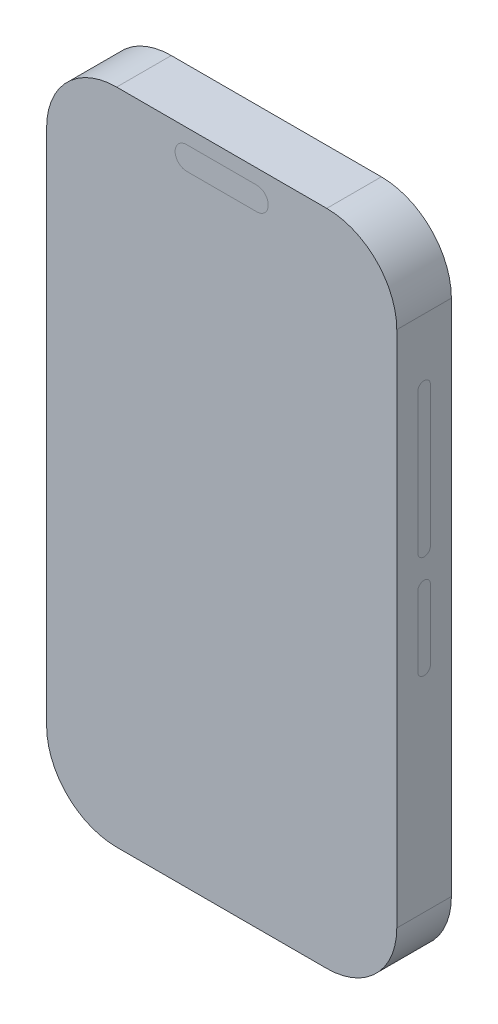
SolidWorks part; units mm, degrees
ref_plane "前视基准面" through (0, 0, 0) normal (0, 0, 1) x (1, 0, 0)
ref_plane "上视基准面" through (0, 0, 0) normal (0, 1, 0) x (1, 0, 0)
ref_plane "右视基准面" through (0, 0, 0) normal (1, 0, 0) x (0, 0, -1)
other "Configuration Table"
sketch "草图2" plane through (0, 0, 0) normal (0, 0, 1) x (1, 0, 0)
  line L1 (-15, 47) -> (15, 47)
  line L2 (-25, 37) -> (-25, -37)
  line L3 (-15, -47) -> (15, -47)
  line L4 (25, 37) -> (25, -37)
  line L5 (-25, 47) -> (25, -47) construction
  line L6 (-25, -47) -> (25, 47) construction
  arc A0 (15, 47) -> (25, 37) centre (15, 37) cw
  arc A1 (-25, -37) -> (-15, -47) centre (-15, -37) ccw
  arc A2 (-15, 47) -> (-25, 37) centre (-15, 37) ccw
  arc A3 (15, -47) -> (25, -37) centre (15, -37) ccw
  point P0 (0, 0)
  dimension "D3" = 10
  dimension "D1" = 50
  dimension "D2" = 94
extrude "凸台-拉伸1" add sketch "草图2" along normal blind 7.8
sketch "草图3" plane through (0, 0, 7.8) normal (0, 0, 1) x (1, 0, 0)
  line L0 (-5, 43.229) -> (5, 43.229) construction
  line L1 (-5, 44.879) -> (5, 44.879)
  line L2 (-5, 41.579) -> (5, 41.579)
  arc A0 (-5, 44.879) -> (-5, 41.579) centre (-5, 43.229) ccw
  arc A1 (5, 41.579) -> (5, 44.879) centre (5, 43.229) ccw
  point P2 (0, 43.229)
  point P7 (0, 0)
  point P8 (0, 0)
split line "分割线1"
sketch "草图7" plane through (25, 0, 0) normal (1, 0, 0) x (0, 0, -1)
  line L0 (-3.8962, 27.8442) -> (-3.8962, 7.8442) construction
  line L1 (-2.9962, 27.8442) -> (-2.9962, 7.8442)
  line L2 (-4.7962, 27.8442) -> (-4.7962, 7.8442)
  arc A0 (-2.9962, 27.8442) -> (-4.7962, 27.8442) centre (-3.8962, 27.8442) ccw
  arc A1 (-4.7962, 7.8442) -> (-2.9962, 7.8442) centre (-3.8962, 7.8442) ccw
  point P2 (-3.8962, 17.8442)
split line "分割线3"
sketch "草图8" plane through (25, 0, 0) normal (1, 0, 0) x (0, 0, -1)
  line L0 (-3.8949, 3.1614) -> (-3.8949, -6.8386) construction
  line L1 (-2.9949, 3.1614) -> (-2.9949, -6.8386)
  line L2 (-4.7949, 3.1614) -> (-4.7949, -6.8386)
  arc A0 (-2.9949, 3.1614) -> (-4.7949, 3.1614) centre (-3.8949, 3.1614) ccw
  arc A1 (-4.7949, -6.8386) -> (-2.9949, -6.8386) centre (-3.8949, -6.8386) ccw
  point P2 (-3.8949, -1.8386)
split line "分割线4"
sketch "草图9" plane through (0, -47, 0) normal (0, -1, 0) x (1, 0, 0)
  line L0 (-4.0922, 3.9187) -> (4.1078, 3.9187) construction
  line L1 (-4.0922, 5.4187) -> (4.1078, 5.4187)
  line L2 (-4.0922, 2.4187) -> (4.1078, 2.4187)
  arc A0 (-4.0922, 5.4187) -> (-4.0922, 2.4187) centre (-4.0922, 3.9187) ccw
  arc A1 (4.1078, 2.4187) -> (4.1078, 5.4187) centre (4.1078, 3.9187) ccw
  point P2 (0.0078, 3.9187)
split line "分割线5"
sketch "草图13" plane through (0, 0, 0) normal (0, 0, -1) x (-1, 0, 0)
  line L1 (-11.6998, 41.476) -> (-7.6998, 41.476)
  line L2 (-17.6998, 35.476) -> (-17.6998, 19.476)
  line L3 (-11.6998, 13.476) -> (-7.6998, 13.476)
  line L4 (-1.6998, 35.476) -> (-1.6998, 19.476)
  arc A0 (-17.6998, 35.476) -> (-11.6998, 41.476) centre (-11.6998, 35.476) cw
  arc A1 (-1.6998, 35.476) -> (-7.6998, 41.476) centre (-7.6998, 35.476) ccw
  arc A2 (-7.6998, 13.476) -> (-1.6998, 19.476) centre (-7.6998, 19.476) ccw
  arc A3 (-11.6998, 13.476) -> (-17.6998, 19.476) centre (-11.6998, 19.476) cw
  circle A5 centre (-12.8662, 23.9064) radius 3
  circle A6 centre (-12.8662, 35.476) radius 3
  circle A7 centre (-4.9143, 29.4727) radius 1.5
  dimension "D1" = 6
  dimension "D2" = 6
  dimension "D3" = 6
  dimension "D4" = 6
split line "分割线6"
